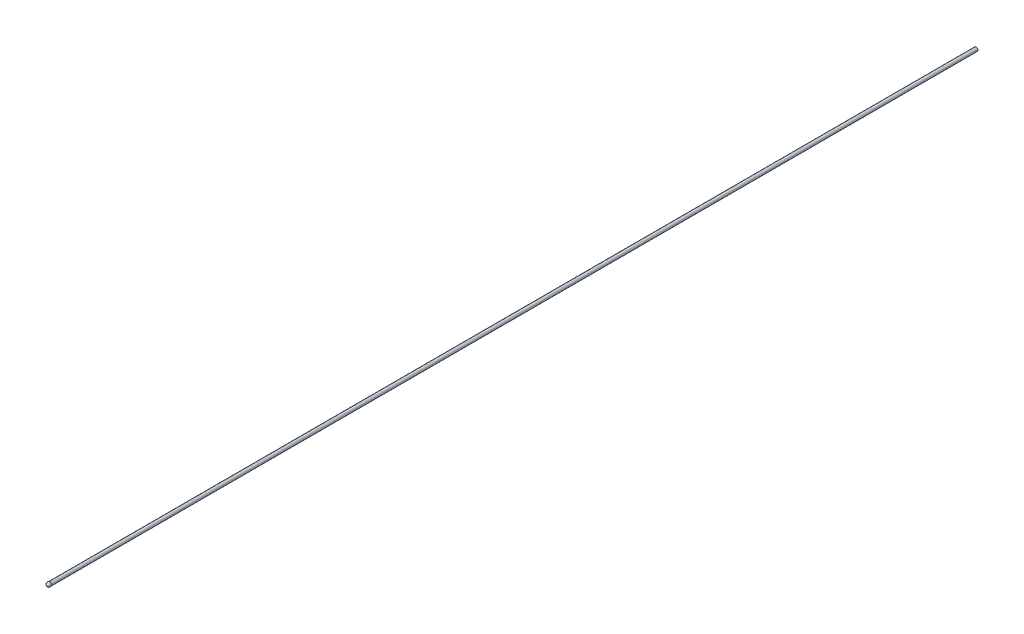
SolidWorks part; units mm, degrees
ref_plane "Front Plane" through (0, 0, 0) normal (0, 0, 1) x (1, 0, 0)
ref_plane "Top Plane" through (0, 0, 0) normal (0, 1, 0) x (1, 0, 0)
ref_plane "Right Plane" through (0, 0, 0) normal (1, 0, 0) x (0, 0, -1)
other "Configuration Table"
sketch "Sketch1" plane through (0, 0, 0) normal (0, 0, 1) x (1, 0, 0)
  circle A0 centre (-1.25, 11.75) radius 1.25
extrude "Boss-Extrude2" add sketch "Sketch1" against normal up to surface (625 mm away)
dome "Dome1" faces to dome 1 distance 2 reverse direction no elliptical dome no face at (0, 11.75, 0) parameters "D1"=2
